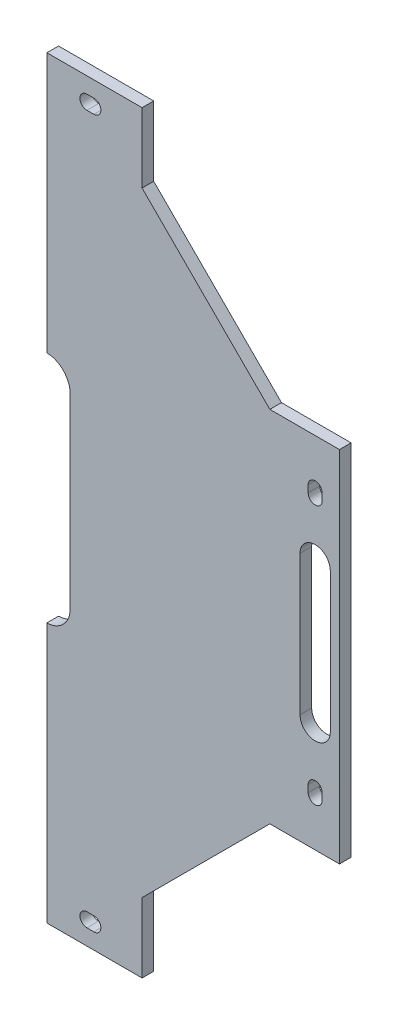
SolidWorks part; units mm, degrees
ref_plane "Front Plane" through (0, 0, 0) normal (0, 0, 1) x (1, 0, 0)
ref_plane "Top Plane" through (0, 0, 0) normal (0, 1, 0) x (1, 0, 0)
ref_plane "Right Plane" through (0, 0, 0) normal (1, 0, 0) x (0, 0, -1)
sketch "Sketch1" plane through (0, 0, 0) normal (0, 0, 1) x (1, 0, 0)
  line L0 (233.2969, -297.5654) -> (233.2969, -621.5654)
  line L1 (233.2969, -621.5654) -> (274.5681, -621.5654)
  line L2 (274.5681, -621.5654) -> (274.5481, -591.5654)
  line L3 (274.5481, -591.5654) -> (329.2969, -536.8167)
  line L4 (329.2969, -536.8167) -> (359.2969, -536.8167)
  line L5 (359.2969, -536.8167) -> (359.2969, -382.3142)
  line L6 (359.2969, -382.3142) -> (329.2969, -382.3142)
  line L7 (329.2969, -382.3142) -> (274.5481, -327.5654)
  line L8 (274.5481, -327.5654) -> (274.5481, -297.5654)
  line L9 (233.2969, -297.5654) -> (274.5481, -297.5654)
  line L10 (243.2969, -419.5654) -> (243.2969, -499.5654)
  arc A0 (243.2969, -419.5654) -> (233.2969, -409.5654) centre (233.2969, -419.5654) ccw
  arc A1 (243.2969, -499.5654) -> (233.2969, -509.5654) centre (233.2969, -499.5654) cw
sketch "Sketch3" plane through (0, 0, 0) normal (0, 0, 1) x (1, 0, 0)
  line L0 (233.2969, -419.5654) -> (233.2969, -499.5654) construction
  line L1 (243.2969, -419.5654) -> (243.2969, -499.5654)
  line L3 (233.2969, -409.5654) -> (233.2969, -509.5654)
  arc A0 (243.2969, -419.5654) -> (233.2969, -409.5654) centre (233.2969, -419.5654) ccw
  arc A1 (233.2969, -509.5654) -> (243.2969, -499.5654) centre (233.2969, -499.5654) ccw
  point P2 (233.2969, -459.5654)
extrude "Boss-Extrude1" add sketch "Sketch1" along normal blind 5 contours L10 A1 L0 L1 L2 L3 L4 L5 L6 L7 L8 L9 A0 region at (287.4847, -459.567, 0)
sketch "Sketch4" plane through (0, 0, 0) normal (0, 0, 1) x (1, 0, 0)
  line L0 (250.6687, -611.5654) -> (253.6687, -611.5654) construction
  line L3 (250.6687, -608.5654) -> (253.6687, -608.5654)
  line L4 (250.6687, -614.5654) -> (253.6687, -614.5654)
  line L5 (359.2969, -459.5654) -> (223.2969, -459.5654)
  line L6 (359.2969, -536.8167) -> (359.2969, -382.3142) construction
  line L7 (250.6687, -307.5654) -> (253.6687, -307.5654) construction
  line L8 (250.6687, -310.5654) -> (253.6687, -310.5654)
  line L9 (250.6687, -304.5654) -> (253.6687, -304.5654)
  line L10 (348.6707, -402.3251) -> (348.6707, -405.3251) construction
  line L11 (351.6707, -402.3251) -> (351.6707, -405.3251)
  line L12 (345.6707, -402.3251) -> (345.6707, -405.3251)
  line L13 (348.6707, -516.8058) -> (348.6707, -513.8058) construction
  line L14 (351.6707, -516.8058) -> (351.6707, -513.8058)
  line L15 (345.6707, -516.8058) -> (345.6707, -513.8058)
  line L16 (348.6707, -429.5654) -> (348.6707, -489.5654) construction
  line L17 (355.1707, -429.5654) -> (355.1707, -489.5654)
  line L18 (342.1707, -429.5654) -> (342.1707, -489.5654)
  line L19 (223.2969, -459.5654) -> (359.2969, -459.5654)
  line L20 (348.6707, -516.8058) -> (348.6707, -513.8058) construction
  line L21 (351.6707, -516.8058) -> (351.6707, -513.8058)
  line L22 (345.6707, -516.8058) -> (345.6707, -513.8058)
  arc A2 (250.6687, -608.5654) -> (250.6687, -614.5654) centre (250.6687, -611.5654) ccw
  arc A3 (253.6687, -614.5654) -> (253.6687, -608.5654) centre (253.6687, -611.5654) ccw
  arc A4 (250.6687, -310.5654) -> (250.6687, -304.5654) centre (250.6687, -307.5654) cw
  arc A5 (253.6687, -304.5654) -> (253.6687, -310.5654) centre (253.6687, -307.5654) cw
  arc A6 (351.6707, -402.3251) -> (345.6707, -402.3251) centre (348.6707, -402.3251) ccw
  arc A7 (345.6707, -405.3251) -> (351.6707, -405.3251) centre (348.6707, -405.3251) ccw
  arc A8 (351.6707, -516.8058) -> (345.6707, -516.8058) centre (348.6707, -516.8058) cw
  arc A9 (345.6707, -513.8058) -> (351.6707, -513.8058) centre (348.6707, -513.8058) cw
  arc A10 (355.1707, -429.5654) -> (342.1707, -429.5654) centre (348.6707, -429.5654) ccw
  arc A11 (342.1707, -489.5654) -> (355.1707, -489.5654) centre (348.6707, -489.5654) ccw
  arc A12 (351.6707, -516.8058) -> (345.6707, -516.8058) centre (348.6707, -516.8058) cw
  arc A13 (345.6707, -513.8058) -> (351.6707, -513.8058) centre (348.6707, -513.8058) cw
  point P2 (252.1687, -611.5654)
  point P13 (252.1687, -307.5654)
  point P20 (348.6707, -403.8251)
  point P27 (348.6707, -515.3058)
  point P34 (348.6707, -459.5654)
  point P41 (348.6707, -515.3058)
extrude "Cut-Extrude5" cut sketch "Sketch4" along normal blind 5 contours L18 A11 L17 A10 | L12 A7 L11 A6 | A2 L4 A3 L3 | L9 A5 L8 A4 | A9 L14 A8 L15
sketch "Sketch8" plane through (0, 0, 5) normal (0, 0, 1) x (1, 0, 0)
  line L13 (233.2969, -297.5654) -> (274.5481, -297.5654) construction
  line L15 (233.2969, -297.5654) -> (274.5481, -297.5654)
  line L16 (233.2969, -297.5654) -> (233.2969, -409.5654) construction
  line L17 (233.2969, -297.5654) -> (233.2969, -409.5654)
  line L18 (274.5481, -327.5654) -> (274.5481, -297.5654) construction
  line L19 (274.5481, -327.5654) -> (274.5481, -297.5654)
  line L20 (233.2969, -509.5654) -> (233.2969, -621.5654) construction
  line L21 (233.2969, -621.5654) -> (274.5681, -621.5654) construction
  line L22 (274.5681, -621.5654) -> (274.5481, -591.5654) construction
  line L23 (274.5481, -591.5654) -> (329.2969, -536.8167) construction
  line L24 (243.4969, -419.5654) -> (243.4969, -499.5654)
  line L25 (233.4969, -509.7635) -> (233.4969, -621.3654)
  line L26 (233.4969, -621.3654) -> (274.368, -621.3654)
  line L27 (274.368, -621.3654) -> (274.3481, -591.4827)
  line L28 (274.3481, -591.4827) -> (329.214, -536.6167)
  line L29 (329.214, -536.6167) -> (359.0969, -536.6167)
  line L30 (359.0969, -536.6167) -> (359.0969, -382.5142)
  line L31 (359.0969, -382.5142) -> (329.214, -382.5142)
  line L32 (329.214, -382.5142) -> (274.3481, -327.6483)
  line L33 (274.3481, -327.6483) -> (274.3481, -297.7654)
  line L34 (274.3481, -297.7654) -> (233.4969, -297.7654)
  line L36 (243.4969, -419.5654) -> (243.4969, -499.5654)
  line L38 (233.4969, -621.3654) -> (274.368, -621.3654)
  line L39 (274.368, -621.3654) -> (274.3481, -591.4827)
  line L40 (274.3481, -591.4827) -> (329.214, -536.6167)
  line L41 (329.214, -536.6167) -> (359.0969, -536.6167)
  line L42 (359.0969, -536.6167) -> (359.0969, -382.5142)
  line L43 (359.0969, -382.5142) -> (329.214, -382.5142)
  line L44 (329.214, -382.5142) -> (274.3481, -327.6483)
  line L45 (274.3481, -327.6483) -> (274.3481, -297.7654)
  line L46 (274.3481, -297.7654) -> (233.4969, -297.7654)
  line L48 (329.2969, -536.8167) -> (359.2969, -536.8167) construction
  line L49 (359.2969, -536.8167) -> (359.2969, -382.3142) construction
  line L50 (359.2969, -382.3142) -> (329.2969, -382.3142) construction
  line L51 (329.2969, -382.3142) -> (274.5481, -327.5654) construction
  line L52 (233.2969, -509.5654) -> (233.2969, -621.5654)
  line L53 (233.2969, -621.5654) -> (274.5681, -621.5654)
  line L54 (274.5681, -621.5654) -> (274.5481, -591.5654)
  line L55 (274.5481, -591.5654) -> (329.2969, -536.8167)
  line L56 (329.2969, -536.8167) -> (359.2969, -536.8167)
  line L57 (359.2969, -536.8167) -> (359.2969, -382.3142)
  line L58 (359.2969, -382.3142) -> (329.2969, -382.3142)
  line L59 (329.2969, -382.3142) -> (274.5481, -327.5654)
  line L60 (233.2969, -409.5654) -> (233.4969, -509.7635)
  line L73 (233.4969, -509.7635) -> (233.4969, -621.3654)
  line L75 (233.4969, -297.7654) -> (233.4969, -409.3674)
  line L76 (233.4969, -297.7654) -> (233.4969, -409.3674)
  arc A7 (233.2969, -509.5654) -> (243.2969, -499.5654) centre (233.2969, -499.5654) ccw construction
  arc A8 (233.2969, -509.5654) -> (243.2969, -499.5654) centre (233.2969, -499.5654) ccw
  arc A9 (233.4969, -509.7635) -> (243.4969, -499.5654) centre (233.2969, -499.5654) ccw
  arc A10 (243.4969, -419.5654) -> (233.4969, -409.3674) centre (233.2969, -419.5654) ccw
  arc A11 (233.4969, -509.7635) -> (243.4969, -499.5654) centre (233.2969, -499.5654) ccw
  arc A12 (243.4969, -419.5654) -> (233.4969, -409.3674) centre (233.2969, -419.5654) ccw
  dimension "D1" = 0.2
sketch3d "3DSketch1"
  line L0 (233.4969, -509.7635, 5) -> (233.4969, -621.3654, 5)
  line L1 (233.4969, -621.3654, 5) -> (274.368, -621.3654, 5)
  line L2 (274.368, -621.3654, 5) -> (274.3481, -591.4827, 5)
  line L3 (274.3481, -591.4827, 5) -> (329.214, -536.6167, 5)
  line L4 (329.214, -536.6167, 5) -> (359.0969, -536.6167, 5)
  line L5 (359.0969, -536.6167, 5) -> (359.0969, -382.5142, 5)
  line L6 (359.0969, -382.5142, 5) -> (329.214, -382.5142, 5)
  line L7 (329.214, -382.5142, 5) -> (274.3481, -327.6483, 5)
  line L8 (274.3481, -327.6483, 5) -> (274.3481, -297.7654, 5)
  line L9 (233.4969, -297.7654, 5) -> (274.3481, -297.7654, 5)
  line L10 (233.4969, -297.7654, 5) -> (233.4969, -409.3674, 5)
  line L11 (243.4969, -419.5654, 5) -> (243.4969, -499.5654, 5)
  line L12 (233.4969, -509.7635, 5) -> (233.4969, -621.3654, 5)
  line L13 (233.4969, -621.3654, 5) -> (274.368, -621.3654, 5)
  line L14 (274.368, -621.3654, 5) -> (274.3481, -591.4827, 5)
  line L15 (274.3481, -591.4827, 5) -> (329.214, -536.6167, 5)
  line L16 (329.214, -536.6167, 5) -> (359.0969, -536.6167, 5)
  line L17 (359.0969, -536.6167, 5) -> (359.0969, -382.5142, 5)
  line L18 (359.0969, -382.5142, 5) -> (329.214, -382.5142, 5)
  line L19 (329.214, -382.5142, 5) -> (274.3481, -327.6483, 5)
  line L20 (274.3481, -327.6483, 5) -> (274.3481, -297.7654, 5)
  line L21 (233.4969, -297.7654, 5) -> (274.3481, -297.7654, 5)
  line L22 (233.4969, -297.7654, 5) -> (233.4969, -409.3674, 5)
  line L23 (243.4969, -419.5654, 5) -> (243.4969, -499.5654, 5)
  line L24 (233.2969, -297.5654, 5) -> (233.2969, -409.5654, 5) construction
  line L25 (233.2969, -297.5654, 5) -> (274.5481, -297.5654, 5) construction
  line L26 (274.5481, -327.5654, 5) -> (274.5481, -297.5654, 5) construction
  line L27 (329.2969, -382.3142, 5) -> (274.5481, -327.5654, 5) construction
  line L28 (359.2969, -382.3142, 5) -> (329.2969, -382.3142, 5) construction
  line L29 (359.2969, -536.8167, 5) -> (359.2969, -382.3142, 5) construction
  line L30 (329.2969, -536.8167, 5) -> (359.2969, -536.8167, 5) construction
  line L31 (274.5481, -591.5654, 5) -> (329.2969, -536.8167, 5) construction
  line L32 (233.2969, -509.5654, 5) -> (233.2969, -621.5654, 5) construction
  line L33 (274.5681, -621.5654, 5) -> (274.5481, -591.5654, 5) construction
  line L34 (233.2969, -621.5654, 5) -> (274.5681, -621.5654, 5) construction
  line L36 (233.2969, -297.5654, 5) -> (233.2969, -409.5654, 5)
  line L37 (233.2969, -297.5654, 5) -> (274.5481, -297.5654, 5)
  line L38 (274.5481, -327.5654, 5) -> (274.5481, -297.5654, 5)
  line L39 (329.2969, -382.3142, 5) -> (274.5481, -327.5654, 5)
  line L40 (359.2969, -382.3142, 5) -> (329.2969, -382.3142, 5)
  line L41 (359.2969, -536.8167, 5) -> (359.2969, -382.3142, 5)
  line L42 (329.2969, -536.8167, 5) -> (359.2969, -536.8167, 5)
  line L43 (274.5481, -591.5654, 5) -> (329.2969, -536.8167, 5)
  line L44 (233.2969, -509.5654, 5) -> (233.2969, -621.5654, 5)
  line L45 (274.5681, -621.5654, 5) -> (274.5481, -591.5654, 5)
  line L46 (233.2969, -621.5654, 5) -> (274.5681, -621.5654, 5)
  line L48 (243.2969, -419.5654, 5) -> (243.2969, -499.5654, 5) construction
  line L49 (243.2969, -419.5654, 5) -> (243.2969, -499.5654, 5)
  arc A0 (243.4969, -499.5654, 5) -> (233.4969, -509.7635, 5) centre (233.2969, -499.5654, 5) ccw
  arc A1 (243.4969, -419.5654, 5) -> (233.4969, -409.3674, 5) centre (233.2969, -419.5654, 5) ccw
  arc A2 (243.4969, -499.5654, 5) -> (233.4969, -509.7635, 5) centre (233.2969, -499.5654, 5) ccw
  arc A3 (243.4969, -419.5654, 5) -> (233.4969, -409.3674, 5) centre (233.2969, -419.5654, 5) ccw
  arc A7 (243.2969, -499.5654, 5) -> (233.2969, -509.5654, 5) centre (233.2969, -499.5654, 5) ccw construction
  arc A10 (243.2969, -499.5654, 5) -> (233.2969, -509.5654, 5) centre (233.2969, -499.5654, 5) ccw
  arc A11 (243.2969, -419.5654, 5) -> (233.2969, -409.5654, 5) centre (233.2969, -419.5654, 5) ccw construction
  arc A12 (243.2969, -419.5654, 5) -> (233.2969, -409.5654, 5) centre (233.2969, -419.5654, 5) ccw
  point P3 (233.2969, -499.5654, -5.2)
  point P17 (233.2969, -419.5654, 15.2)
  point P18 (233.2969, -499.5654, -5.2)
  point P19 (233.2969, -419.5654, 15.2)
  point P31 (233.2969, -499.5654, -5)
  point P33 (233.2969, -499.5654, -5)
  point P40 (233.2969, -419.5654, 15)
  point P41 (233.2969, -419.5654, 15)
  dimension "D1" = 0.2
extrude "Cut-Extrude6" cut sketch "Sketch8" against normal blind 5 rebuild error yes
sketch "Sketch10" plane through (0, 0, 5) normal (0, 0, 1) x (1, 0, 0)
sketch "Sketch11" plane through (0, 0, 5) normal (0, 0, 1) x (1, 0, 0)
sketch "Sketch12" plane through (0, 0, 5) normal (0, 0, 1) x (1, 0, 0)
  line L0 (243.4969, -419.5654) -> (243.4969, -499.5654)
  line L1 (233.4969, -509.7635) -> (233.4969, -621.3654)
  line L2 (233.4969, -621.3654) -> (274.368, -621.3654)
  line L3 (274.368, -621.3654) -> (274.3481, -591.4827)
  line L4 (274.3481, -591.4827) -> (329.214, -536.6167)
  line L5 (329.214, -536.6167) -> (359.0969, -536.6167)
  line L6 (359.0969, -536.6167) -> (359.0969, -382.5142)
  line L7 (359.0969, -382.5142) -> (329.214, -382.5142)
  line L8 (329.214, -382.5142) -> (274.3481, -327.6483)
  line L9 (274.3481, -327.6483) -> (274.3481, -297.7654)
  line L10 (274.3481, -297.7654) -> (233.4969, -297.7654)
  line L11 (233.4969, -297.7654) -> (233.4969, -409.3674)
  line L12 (243.2969, -419.5654) -> (243.2969, -499.5654)
  line L13 (233.2969, -509.5654) -> (233.2969, -621.5654)
  line L14 (233.2969, -621.5654) -> (274.5681, -621.5654)
  line L15 (274.5681, -621.5654) -> (274.5481, -591.5654)
  line L16 (274.5481, -591.5654) -> (329.2969, -536.8167)
  line L17 (329.2969, -536.8167) -> (359.2969, -536.8167)
  line L18 (359.2969, -536.8167) -> (359.2969, -382.3142)
  line L19 (359.2969, -382.3142) -> (329.2969, -382.3142)
  line L20 (329.2969, -382.3142) -> (274.5481, -327.5654)
  line L21 (274.5481, -327.5654) -> (274.5481, -297.5654)
  line L22 (274.5481, -297.5654) -> (233.2969, -297.5654)
  line L23 (233.2969, -297.5654) -> (233.2969, -409.5654)
  line L24 (243.2969, -419.5654) -> (243.2969, -499.5654)
  line L25 (233.2969, -509.5654) -> (233.2969, -621.5654)
  line L26 (233.2969, -621.5654) -> (274.5681, -621.5654)
  line L27 (274.5681, -621.5654) -> (274.5481, -591.5654)
  line L28 (274.5481, -591.5654) -> (329.2969, -536.8167)
  line L29 (329.2969, -536.8167) -> (359.2969, -536.8167)
  line L30 (359.2969, -536.8167) -> (359.2969, -382.3142)
  line L31 (359.2969, -382.3142) -> (329.2969, -382.3142)
  line L32 (329.2969, -382.3142) -> (274.5481, -327.5654)
  line L33 (274.5481, -327.5654) -> (274.5481, -297.5654)
  line L34 (274.5481, -297.5654) -> (233.2969, -297.5654)
  line L35 (233.2969, -297.5654) -> (233.2969, -409.5654)
  arc A0 (233.4969, -509.7635) -> (243.4969, -499.5654) centre (233.2969, -499.5654) ccw
  arc A1 (243.4969, -419.5654) -> (233.4969, -409.3674) centre (233.2969, -419.5654) ccw
  arc A2 (233.2969, -509.5654) -> (243.2969, -499.5654) centre (233.2969, -499.5654) ccw
  arc A3 (243.2969, -419.5654) -> (233.2969, -409.5654) centre (233.2969, -419.5654) ccw
  arc A4 (233.2969, -509.5654) -> (243.2969, -499.5654) centre (233.2969, -499.5654) ccw
  arc A5 (243.2969, -419.5654) -> (233.2969, -409.5654) centre (233.2969, -419.5654) ccw
  dimension "D1" = 0
  dimension "D2" = 0.2
extrude "Cut-Extrude7" cut sketch "Sketch12" against normal blind 10
